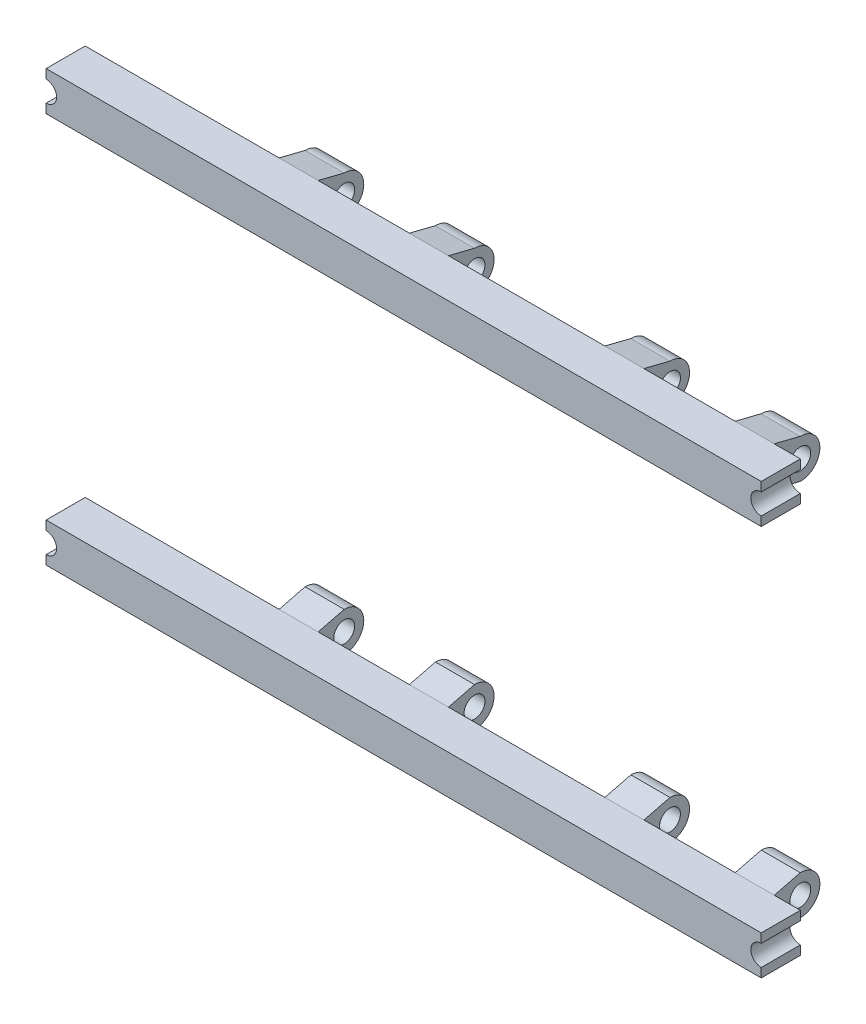
SolidWorks part; units mm, degrees
ref_plane "Front Plane" through (0, 0, 0) normal (0, 0, 1) x (1, 0, 0)
ref_plane "Top Plane" through (0, 0, 0) normal (0, 1, 0) x (1, 0, 0)
ref_plane "Right Plane" through (0, 0, 0) normal (1, 0, 0) x (0, 0, -1)
sketch "Sketch1" plane through (0, 0, 0) normal (0, 0, 1) x (1, 0, 0)
  line L1 (3, -220) -> (112.75, -220)
  line L2 (3, -220) -> (3, -214)
  line L3 (3, -214) -> (112.75, -214)
  line L4 (112.75, -220) -> (112.75, -214)
  line L6 (3, -214) -> (112.75, -220) construction
  line L7 (57.875, -217) -> (57.875, -159) construction
  line L8 (3, -159) -> (112.75, -159) construction
  line L10 (3, -154) -> (112.75, -154)
  line L11 (3, -154) -> (3, -160)
  line L12 (3, -160) -> (112.75, -160)
  line L13 (112.75, -154) -> (112.75, -160)
  point P12 (57.875, -159)
  dimension "D1" = 58
extrude "Boss-Extrude1" add sketch "Sketch1" against normal blind 6 contours L12 L13 L10 L11 | L1 L4 L3 L2
sketch "Sketch2" plane through (112.75, 0, 0) normal (1, 0, 0) x (0, 0, -1)
  line L0 (6, -214) -> (10, -213)
  line L1 (6, -220) -> (10, -219)
  line L2 (6, -220) -> (6, -214)
  line L3 (6, -214) -> (6, -160) construction
  line L4 (6, -187) -> (28.8077, -187) construction
  line L5 (6, -154) -> (6, -160)
  line L6 (6, -154) -> (10, -155)
  line L7 (6, -160) -> (10, -161)
  circle A0 centre (10, -216) radius 1.6
  arc A1 (8.5882, -160.6471) -> (10, -161) centre (10, -158) cw
  arc A2 (8.5882, -213.3529) -> (10, -213) centre (10, -216) ccw
  circle A3 centre (10, -158) radius 1.6
  line M9 (6, -160) -> (6, -154)
  dimension "D1" = 3.2
  dimension "D2" = 6
  dimension "D3" = 58
  dimension "D4" = 4
extrude "Boss-Extrude2" add sketch "Sketch2" against normal blind 6 from offset 4 contours L0 A2 A0 | A2 L0 L2 L1 | A1 L7 A3 | L7 A1 L6 M9 region at (112.75, -217.181, -6.9787) region at (112.75, -213.2588, -9.3147) region at (112.75, -156.819, -6.9787) region at (112.75, -158, -12.9151) offset against normal yes
pattern_linear "LPattern1" count 8 spacing 10 along (-1, 0, 0) skipping (1, 0), (3, 0), (4, 0), (6, 0) of "Boss-Extrude2"
sketch "Sketch3" plane through (0, 0, 0) normal (0, 0, 1) x (1, 0, 0)
  line L0 (3, -220) -> (3, -214) construction
  line L1 (3, -154) -> (3, -160) construction
  line L2 (112.75, -154) -> (112.75, -160) construction
  line L4 (112.75, -220) -> (112.75, -214) construction
  circle A0 centre (3, -217) radius 1.6
  circle A1 centre (3, -157) radius 1.6
  circle A2 centre (112.75, -157) radius 1.6
  circle A3 centre (112.75, -217) radius 1.6
  dimension "D1" = 3.2
extrude "Cut-Extrude1" cut sketch "Sketch3" against normal up to next
